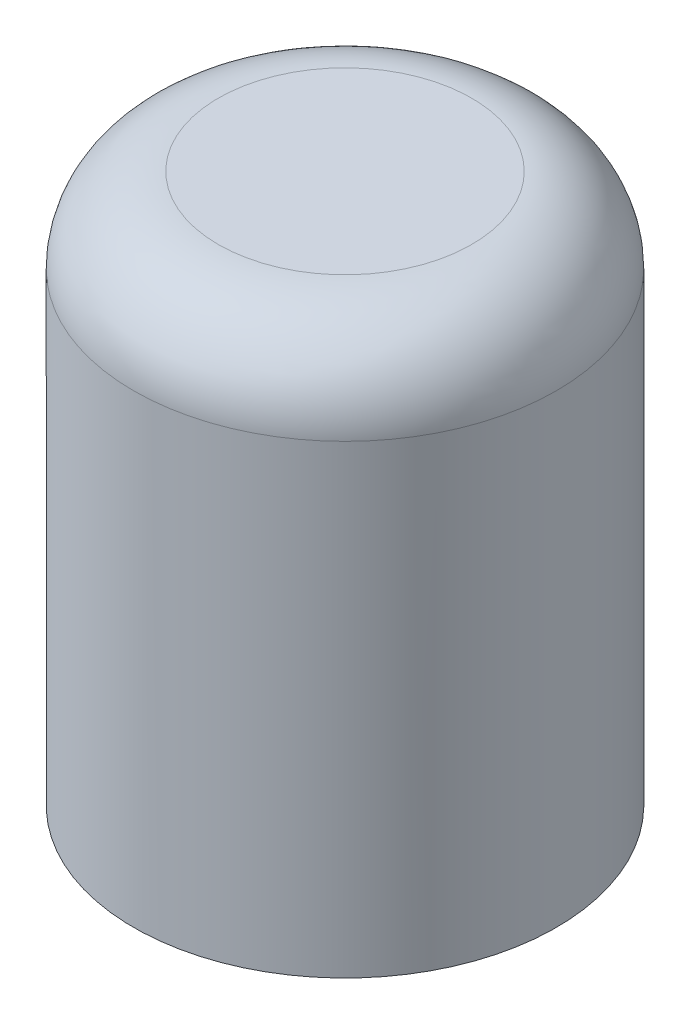
SolidWorks part; units mm, degrees
ref_plane "Front Plane" through (0, 0, 0) normal (0, 0, 1) x (1, 0, 0)
ref_plane "Top Plane" through (0, 0, 0) normal (0, 1, 0) x (1, 0, 0)
ref_plane "Right Plane" through (0, 0, 0) normal (1, 0, 0) x (0, 0, -1)
sketch "Sketch1" plane through (0, 0, 0) normal (0, 1, 0) x (1, 0, 0)
  circle A0 centre (0, 0) radius 5
  dimension "D1" = 10
extrude "Boss-Extrude1" add sketch "Sketch1" along normal blind 13
sketch "Insert" plane through (0, 0, 0) normal (0, -1, 0) x (1, 0, 0)
  line L0 (-1.6, 3) -> (-1.6, -3)
  line L1 (3.4, 0) -> (1.7771, 0) construction
  line L2 (-1.6, 0) -> (-0.8194, 0) construction
  arc A0 (-1.6, -3) -> (-1.6, 3) centre (0, 0) ccw
  dimension "D1" = 6
  dimension "D2" = 5
extrude "Cut-Extrude1" cut sketch "Insert" against normal blind 12.5
fillet "Fillet4" radius 2 2 edges at (3.4, 12.5, 0) (-1.6, 12.5, 0) type face fillet first side face at (-1.6, 6.25, 0) first side face at (0.9, 6.25, 0) second side face at (0.9, 12.5, 0)
fillet "Fillet5" radius 0.5 2 edges at (-1.6, 0, 0) (3.4, 0, 0) type face fillet first side face at (0.9, 0, 0) second side face at (0.9, 5.25, 0) second side face at (-1.6, 5.25, 0)
sketch "Sketch2" [suppressed] plane through (0, 13, 0) normal (0, 1, 0) x (1, 0, 0)
  line L1 (0, 5.7735) -> (-5, 2.8868)
  line L2 (-5, 2.8868) -> (-5, -2.8868)
  line L3 (-5, -2.8868) -> (0, -5.7735)
  line L4 (0, -5.7735) -> (5, -2.8868)
  line L5 (5, -2.8868) -> (5, 2.8868)
  line L6 (5, 2.8868) -> (0, 5.7735)
  circle A0 centre (0, 0) radius 5 construction
  circle A1 centre (0, 0) radius 5 construction
  circle A2 centre (0, 0) radius 4.75
  dimension "D1" = 9.5
extrude "Boss-Extrude2" [suppressed] add sketch "Sketch2" against normal up to surface (13 mm away)
fillet "Fillet6" [suppressed] radius 2 type face fillet
fillet "Round Body" radius 2 1 edges at (0, 13, 5) type face fillet first side face at (0, 13, 5) second side face at (0, 13, 5)
